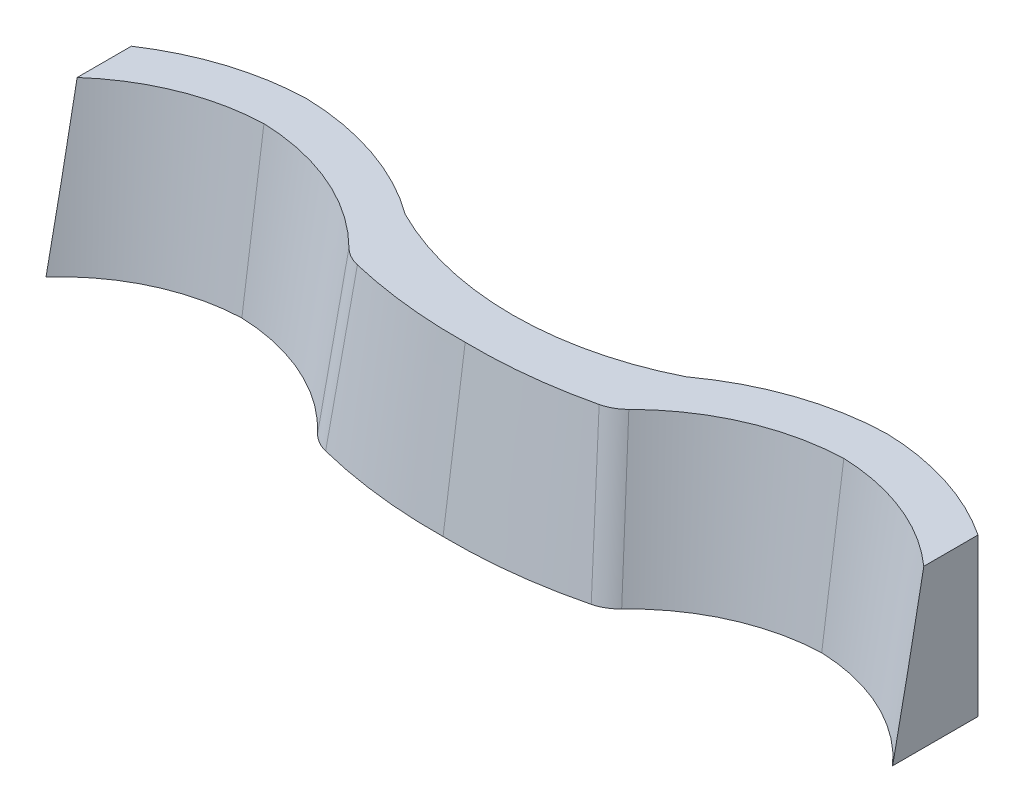
SolidWorks part; units mm, degrees
ref_plane "Front Plane" through (0, 0, 0) normal (0, 0, 1) x (1, 0, 0)
ref_plane "Top Plane" through (0, 0, 0) normal (0, 1, 0) x (1, 0, 0)
ref_plane "Right Plane" through (0, 0, 0) normal (1, 0, 0) x (0, 0, -1)
sketch "Sketch1" plane through (0, 0, 0) normal (0, 1, 0) x (1, 0, 0)
  line L0 (-110, -30) -> (-110, -41.2422) construction
  line L1 (-39.8399, -30) -> (34.8399, -30) construction
  line L2 (110, -30) -> (110, -41.2422) construction
  line L3 (0, -142.6423) -> (0, 36.4059) construction
  line L4 (0, -100) -> (0, 70) construction
  line L5 (-42.9151, -50) -> (42.9151, -50) construction
  line L6 (-110, -41.2422) -> (-39.8399, -43.9889) construction
  line L7 (39.8399, -43.9889) -> (110, -41.2422) construction
  line L8 (-110, -30) -> (-39.8399, -30) construction
  line L9 (110, -30) -> (34.8399, -30) construction
  line L10 (-39.8399, -30) -> (-39.8399, -43.9889) construction
  line L11 (34.8399, -30) -> (39.8399, -43.9889) construction
  arc A0 (-39.8399, -30) -> (34.8399, -30) centre (-2.5, 38.0274) ccw construction
  arc A1 (-39.8399, -43.9889) -> (0, -50) centre (-1.9011, 72.4289) ccw construction
  arc A2 (39.8399, -43.9889) -> (0, -50) centre (1.9011, 72.4289) cw construction
  dimension "D1" = 77.6015
  dimension "D2" = 122.4436
  dimension "D3" = 34.8399
  dimension "D4" = 70.1601
  dimension "D5" = 70.1601
  dimension "D6" = 92.242
  dimension "D7" = 13.9889
ref_plane "Bottom Of Chassis" through (0, -15, 0) normal (0, 1, 0) x (1, 0, 0)
ref_plane "Top of Chassis" through (0, 24, 0) normal (0, 1, 0) x (1, 0, 0)
sketch "Sketch3" plane through (0, 24, 0) normal (0, 1, 0) x (1, 0, 0)
  line L6 (-71.9147, -28) -> (-71.9147, -17.3273) construction
  line L7 (0, -50) -> (0, -57.8303) construction
  line L8 (0, -142.6423) -> (0, 36.4059) construction
  line L9 (105, -41.2425) -> (105, -27.799)
  line L10 (-88.5863, -28) -> (-55.2431, -28) construction
  line L11 (-105, -41.2425) -> (-105, -27.799)
  line L12 (-71.9147, -17.3273) -> (71.9147, -17.3273) construction
  line L13 (71.9147, -28) -> (71.9147, -17.3273) construction
  line L14 (32.8884, -46.0288) -> (-32.8884, -46.0288) construction
  arc A0 (-34.8399, -30) -> (34.8399, -30) centre (0, 39.341) ccw
  arc A1 (0, -50) -> (32.8884, -46.0288) centre (1.9011, 72.4289) ccw
  arc A2 (-32.8884, -46.0288) -> (-71.9147, -28) centre (-73.6989, -83.1159) ccw
  arc A3 (-71.9147, -28) -> (-105, -41.2425) centre (-70.2175, -80.192) ccw
  arc A4 (71.9147, -28) -> (105, -41.2425) centre (70.2175, -80.192) cw
  arc A5 (71.9147, -17.3273) -> (105, -27.799) centre (70.2175, -80.192) cw
  arc A6 (-34.8399, -30) -> (-71.9147, -17.3273) centre (-73.6989, -83.1159) ccw
  arc A7 (-71.9147, -17.3273) -> (-105, -27.799) centre (-70.2175, -80.192) ccw
  arc A8 (-71.9147, -17.3273) -> (-112.1058, -33.2855) centre (-70.2175, -80.192) ccw construction
  arc A9 (-27.3251, -36.417) -> (-71.9147, -17.3273) centre (-73.6989, -83.1159) ccw construction
  arc A10 (34.8399, -30) -> (71.9147, -17.3273) centre (73.6989, -83.1159) cw
  arc A11 (32.8884, -46.0288) -> (71.9147, -28) centre (73.6989, -83.1159) cw
  arc A12 (-34.8399, -30) -> (34.8399, -30) centre (0, 39.341) ccw construction
  arc A16 (0, -50) -> (39.8399, -43.9889) centre (1.9011, 72.4289) ccw construction
  arc A18 (-32.8884, -46.0288) -> (0, -50) centre (-1.9011, 72.4289) ccw
  arc A19 (-39.8399, -43.9889) -> (0, -50) centre (-1.9011, 72.4289) ccw construction
  arc A21 (-27.3251, -36.417) -> (0, -39.3306) centre (-1.9011, 72.4289) ccw construction
  arc A22 (0, -39.3306) -> (30.1886, -35.7081) centre (1.9011, 72.4289) ccw construction
  point P32 (0, 0)
  dimension "D1" = 10.668
extrude "Boss-Extrude1" add sketch "Sketch3" against normal up to surface (39 mm away) contours A2 A18 A1 A11 A4 L9 A5 A10 A0 A6 A7 L11 A3 region at (90.4117, 24, 29.7385) up to plane "Bottom Of Chassis"
draft "Draft2" type of draft neutral plane draft angle 8 faces to draft 6 face at (89.0397, 4.5, 33.1664) face at (51.487, 4.5, 35.0346) face at (16.5117, 4.5, 48.5731) face at (-89.0397, 4.5, 33.1664) face at (-51.487, 4.5, 35.0346) face at (-16.5117, 4.5, 48.5731) neutral plane through (0, 24, 0) neutral plane normal (0, 1, 0) parameters "D1"=8
fillet "Fillet1" radius 10 2 edges
